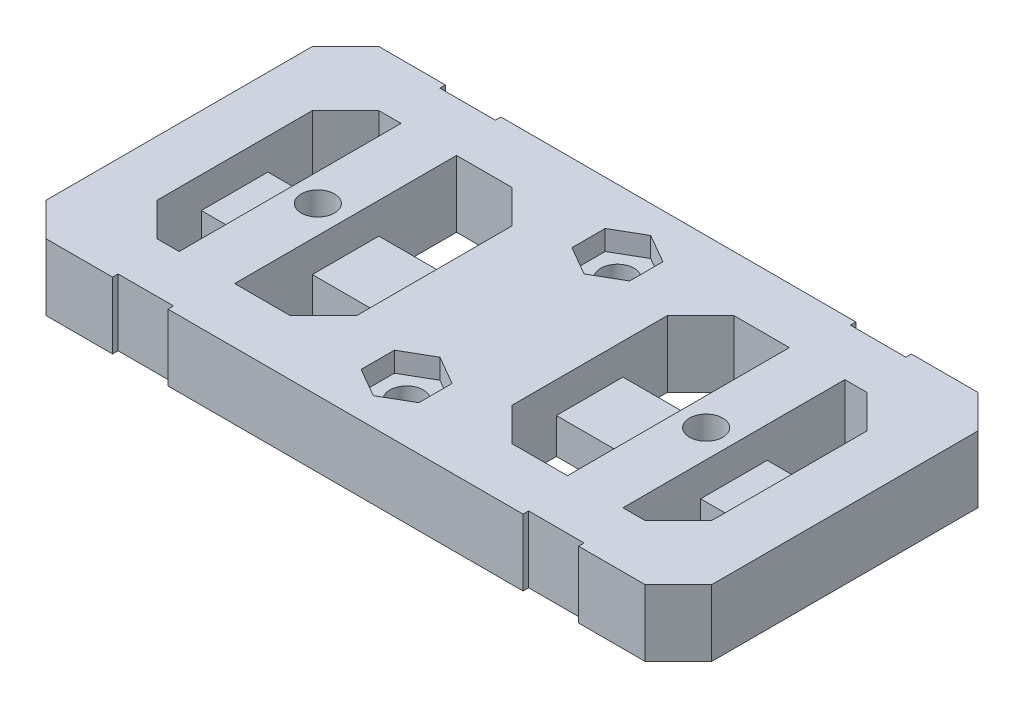
SolidWorks part; units mm, degrees
ref_plane "정면" through (0, 0, 0) normal (0, 0, 1) x (1, 0, 0)
ref_plane "윗면" through (0, 0, 0) normal (0, 1, 0) x (1, 0, 0)
ref_plane "우측면" through (0, 0, 0) normal (1, 0, 0) x (0, 0, -1)
sketch "스케치1" plane through (0, 0, 0) normal (0, 1, 0) x (1, 0, 0)
  line L0 (0, -9.5) -> (0, 9.5) construction
  line L1 (25, 10) -> (25, -10)
  line L2 (0, 12.5022) -> (-2.6, 11.0011)
  line L3 (-2.6, 11.0011) -> (-2.6, 7.9989)
  line L4 (-2.6, 7.9989) -> (0, 6.4978)
  line L5 (0, 6.4978) -> (2.6, 7.9989)
  line L6 (2.6, 7.9989) -> (2.6, 11.0011)
  line L7 (2.6, 11.0011) -> (0, 12.5022)
  line L8 (0, -6.4978) -> (-2.6, -7.9989)
  line L9 (-2.6, -7.9989) -> (-2.6, -11.0011)
  line L10 (-2.6, -11.0011) -> (0, -12.5022)
  line L11 (0, -12.5022) -> (2.6, -11.0011)
  line L12 (2.6, -11.0011) -> (2.6, -7.9989)
  line L13 (2.6, -7.9989) -> (0, -6.4978)
  line L14 (-30, -15) -> (30, -15)
  line L15 (-30, -15) -> (-30, 15)
  line L16 (-30, 15) -> (30, 15)
  line L17 (30, -15) -> (30, 15)
  line L18 (-30, -15) -> (30, 15) construction
  line L19 (-30, 15) -> (30, -15) construction
  line L20 (-25, 10) -> (-7, 10)
  line L21 (-25, 10) -> (-25, -10)
  line L22 (-25, -10) -> (-7, -10)
  line L23 (-7, 10) -> (-7, -10)
  line L24 (25, 10) -> (7, 10)
  line L25 (7, 10) -> (7, -10)
  line L26 (25, -10) -> (7, -10)
  circle A0 centre (0, 9.5) radius 1.5
  circle A1 centre (0, -9.5) radius 1.5
  circle A2 centre (0, 9.5) radius 2.6 construction
  circle A3 centre (0, -9.5) radius 2.6 construction
  point P4 (0, 0)
  point P7 (0, 0)
  point P34 (-7, 0)
  point P35 (7, 0)
  point P36 (-30, 0)
  point P37 (30, 0)
  dimension "D2" = 3
  dimension "D1" = 19
  dimension "D3" = 5.2
  dimension "D4" = 30
  dimension "D5" = 60
  dimension "D6" = 18
  dimension "D7" = 20
  dimension "D8" = 5
extrude "보스-돌출1" add sketch "스케치1" along normal blind 3 contours L14 L17 L16 L15 L7 L6 L5 L4 L3 L2 L13 L12 L11 L10 L9 L8 L20 L23 L22 L21 L1 L26 L25 L24 | L12 L13 L8 L9 L10 L11 A1 | L6 L7 L2 L3 L4 L5 A0 region at (1.2603, 0, -11.6829) region at (1.2603, 0, 7.3171) region at (0, 0, 0)
extrude "컷-돌출1" cut sketch "스케치1<3>" against normal blind 1.8 from surface contours L12 L13 L8 L9 L10 L11 A1 | L6 L7 L2 L3 L4 L5 A0 region at (1.2603, 0, -11.6829) region at (1.2603, 0, 7.3171) starting at face at (0, 3, 0)
sketch "스케치1<3>" plane through (0, 0, 0) normal (0, 1, 0) x (1, 0, 0) same geometry as "스케치1"
chamfer "모따기1" distance 3 angle 45 12 edges at (25, 1.5, -10) (25, 1.5, 10) (7, 1.5, 10) (7, 1.5, -10) (-25, 1.5, 10) (-7, 1.5, 10) (-7, 1.5, -10) (-25, 1.5, -10) (30, 1.5, -15) (30, 1.5, 15) (-30, 1.5, 15) (-30, 1.5, -15)
sketch "스케치2" plane through (0, 3, 0) normal (0, 1, 0) x (1, 0, 0)
  line L0 (0, 45) -> (0, -15)
  line L2 (-27, -15) -> (27, -15) construction
  line L3 (-27, 15) -> (27, 15) construction
  line L4 (-21, 15) -> (-16, 15)
  line L5 (-21, 15) -> (-21, 14.5)
  line L6 (-21, 14.5) -> (-16, 14.5)
  line L7 (-16, 15) -> (-16, 14.5)
  line L8 (21, 15) -> (21, 14.5)
  line L9 (21, 15) -> (16, 15)
  line L10 (16, 15) -> (16, 14.5)
  line L11 (21, 14.5) -> (16, 14.5)
  line L12 (21, -15) -> (21, -14.5)
  line L13 (-21, -15) -> (-16, -15)
  line L14 (-21, -15) -> (-21, -14.5)
  line L15 (-21, -14.5) -> (-16, -14.5)
  line L16 (-16, -15) -> (-16, -14.5)
  line L17 (21, -15) -> (16, -15)
  line L18 (16, -15) -> (16, -14.5)
  line L19 (21, -14.5) -> (16, -14.5)
  line L20 (-30, -12) -> (-30, 12) construction
  point P3 (0, 15)
  line M16 (27, 15) -> (-27, 15)
  line M20 (-27, -15) -> (27, -15)
  dimension "D1" = 0.5
  dimension "D2" = 9
  dimension "D3" = 5
extrude "컷-돌출2" cut sketch "스케치2" against normal through all contours L16 L15 L14 M20 | L12 L19 L18 M20 | L11 L8 L10 M16 | L4 L7 L6 L5 region at (18.5, 3, 14.75) region at (-18.5, 3, 14.75) region at (18.5, 3, -14.75)
sketch "스케치3" plane through (0, 3, 0) normal (0, 1, 0) x (1, 0, 0)
  line L0 (0, 15) -> (0, -15) construction
  line L1 (-16, 15) -> (16, 15) construction
  line L2 (-16, -15) -> (16, -15) construction
  line L3 (-30, 0) -> (30, 0) construction
  line L4 (-30, -12) -> (-30, 12) construction
  line L5 (30, -12) -> (30, 12) construction
  line L6 (-22, 10) -> (-10, 10) construction
  line L7 (-20, -10) -> (-15, -10)
  line L8 (-20, -10) -> (-20, 10)
  line L9 (-20, 10) -> (-15, 10)
  line L10 (-15, -10) -> (-15, 10)
  line L11 (-20, -10) -> (-15, 10) construction
  line L12 (-20, 10) -> (-15, -10) construction
  line L13 (20, -10) -> (15, 10) construction
  line L14 (20, 10) -> (15, -10) construction
  line L15 (20, -10) -> (20, 10)
  line L16 (20, -10) -> (15, -10)
  line L17 (15, -10) -> (15, 10)
  line L18 (20, 10) -> (15, 10)
  circle A0 centre (-17.5, 0) radius 1.5
  circle A1 centre (17.5, 0) radius 1.5
  point P24 (17.5, 0)
  dimension "D1" = 3
  dimension "D2" = 35
  dimension "D3" = 5
extrude "보스-돌출2" add sketch "스케치3" against normal up to vertex (3 mm away) up to point (-10, 0, -10)
sketch "스케치4" plane through (0, 0, 0) normal (0, -1, 0) x (1, 0, 0)
  line L0 (-22, 10) -> (-20, 10) construction
  line L1 (-20, -10) -> (-20, 10) construction
  line L2 (-25, -7) -> (-25, 7) construction
  line L3 (-22, 10) -> (-20, 10)
  line L4 (-20, -10) -> (-20, 10)
  line L5 (-25, -7) -> (-25, 7)
  line L6 (-20, -10) -> (-20, 10)
  line L7 (-22, -10) -> (-20, -10)
  line L8 (-25, -7) -> (-22, -10)
  line L9 (-25, 7) -> (-25, -7)
  line L10 (-22, 10) -> (-25, 7)
  line L11 (-20, 10) -> (-22, 10)
  line L12 (-20, -10) -> (-20, 10)
  line L13 (-22, -10) -> (-20, -10)
  line L14 (-25, -7) -> (-22, -10)
  line L15 (-25, 7) -> (-25, -7)
  line L16 (-22, 10) -> (-25, 7)
  line L17 (-20, 10) -> (-22, 10)
  line L18 (-15, -10) -> (-10, -10)
  line L19 (-15, 10) -> (-15, -10)
  line L20 (-10, 10) -> (-15, 10)
  line L21 (-7, 7) -> (-10, 10)
  line L22 (-7, -7) -> (-7, 7)
  line L23 (-10, -10) -> (-7, -7)
  line L24 (-27, -15) -> (-21, -15)
  line L25 (-21, -15) -> (-21, -14.5)
  line L26 (-21, -14.5) -> (-16, -14.5)
  line L27 (-16, -14.5) -> (-16, -15)
  line L28 (-16, -15) -> (16, -15)
  line L29 (16, -15) -> (16, -14.5)
  line L30 (16, -14.5) -> (21, -14.5)
  line L31 (21, -14.5) -> (21, -15)
  line L32 (21, -15) -> (27, -15)
  line L33 (27, -15) -> (30, -12)
  line L34 (30, -12) -> (30, 12)
  line L35 (30, 12) -> (27, 15)
  line L36 (27, 15) -> (21, 15)
  line L37 (21, 15) -> (21, 14.5)
  line L38 (21, 14.5) -> (16, 14.5)
  line L39 (16, 14.5) -> (16, 15)
  line L40 (16, 15) -> (-16, 15)
  line L41 (-16, 15) -> (-16, 14.5)
  line L42 (-16, 14.5) -> (-21, 14.5)
  line L43 (-21, 14.5) -> (-21, 15)
  line L44 (-21, 15) -> (-27, 15)
  line L45 (-27, 15) -> (-30, 12)
  line L46 (-30, 12) -> (-30, -12)
  line L47 (-30, -12) -> (-27, -15)
  line L48 (-27, -15) -> (-21, -15)
  line L49 (-21, -15) -> (-21, -14.5)
  line L50 (-21, -14.5) -> (-16, -14.5)
  line L51 (-16, -14.5) -> (-16, -15)
  line L52 (-16, -15) -> (16, -15)
  line L53 (16, -15) -> (16, -14.5)
  line L54 (16, -14.5) -> (21, -14.5)
  line L55 (21, -14.5) -> (21, -15)
  line L56 (21, -15) -> (27, -15)
  line L57 (27, -15) -> (30, -12)
  line L58 (30, -12) -> (30, 12)
  line L59 (30, 12) -> (27, 15)
  line L60 (27, 15) -> (21, 15)
  line L61 (21, 15) -> (21, 14.5)
  line L62 (21, 14.5) -> (16, 14.5)
  line L63 (16, 14.5) -> (16, 15)
  line L64 (16, 15) -> (-16, 15)
  line L65 (-16, 15) -> (-16, 14.5)
  line L66 (-16, 14.5) -> (-21, 14.5)
  line L67 (-21, 14.5) -> (-21, 15)
  line L68 (-21, 15) -> (-27, 15)
  line L69 (-27, 15) -> (-30, 12)
  line L70 (-30, 12) -> (-30, -12)
  line L71 (-30, -12) -> (-27, -15)
  line L72 (-15, -10) -> (-10, -10)
  line L73 (-15, 10) -> (-15, -10)
  line L74 (-10, 10) -> (-15, 10)
  line L75 (-7, 7) -> (-10, 10)
  line L76 (-7, -7) -> (-7, 7)
  line L77 (-10, -10) -> (-7, -7)
  line L78 (15, 10) -> (10, 10)
  line L79 (15, -10) -> (15, 10)
  line L80 (10, -10) -> (15, -10)
  line L81 (7, -7) -> (10, -10)
  line L82 (7, 7) -> (7, -7)
  line L83 (10, 10) -> (7, 7)
  line L84 (15, 10) -> (10, 10)
  line L85 (15, -10) -> (15, 10)
  line L86 (10, -10) -> (15, -10)
  line L87 (7, -7) -> (10, -10)
  line L88 (7, 7) -> (7, -7)
  line L89 (10, 10) -> (7, 7)
  line L90 (20, 10) -> (20, -10)
  line L91 (22, 10) -> (20, 10)
  line L92 (25, 7) -> (22, 10)
  line L93 (25, -7) -> (25, 7)
  line L94 (22, -10) -> (25, -7)
  line L95 (20, -10) -> (22, -10)
  line L96 (20, 10) -> (20, -10)
  line L97 (22, 10) -> (20, 10)
  line L98 (25, 7) -> (22, 10)
  line L99 (25, -7) -> (25, 7)
  line L100 (22, -10) -> (25, -7)
  line L101 (20, -10) -> (22, -10)
  line L102 (-30, 0) -> (30, 0) construction
  line L103 (-25, -3) -> (25, -3)
  line L104 (-25, -3) -> (-25, 3)
  line L105 (-25, 3) -> (25, 3)
  line L106 (25, -3) -> (25, 3)
  circle A0 centre (0, 9.5) radius 2.75
  circle A1 centre (-17.5, 0) radius 1.5
  circle A2 centre (-17.5, 0) radius 1.5
  circle A3 centre (17.5, 0) radius 1.5
  circle A4 centre (17.5, 0) radius 1.5
  circle A5 centre (0, -9.5) radius 1.5
  circle A6 centre (0, -9.5) radius 1.5
  circle A7 centre (0, 9.5) radius 1.5
  circle A8 centre (0, 9.5) radius 1.5
  circle A9 centre (0, -9.5) radius 2.75
  circle A10 centre (-17.5, 0) radius 2.75
  circle A11 centre (17.5, 0) radius 2.75
  dimension "D10" = 5.5
  dimension "D11" = 6
  dimension "D1" = 0
  dimension "D2" = 0
  dimension "D3" = 0
  dimension "D4" = 0
  dimension "D5" = 0
  dimension "D6" = 0
  dimension "D7" = 0
  dimension "D8" = 0
  dimension "D9" = 0
extrude "보스-돌출3" add sketch "스케치4" along normal blind 3 contours L70 L102 L104 L5 L16 L3 L4 L105 L73 L74 L75 L76 L88 L89 L84 L85 L96 L97 L98 L99 L106 L58 L59 L60 L61 L62 L63 L64 L65 L66 L67 L68 L69 A0 | L102 L70 L71 L48 L49 L50 L51 L52 L53 L54 L55 L56 L57 L58 L99 L100 L101 L96 L103 L85 L86 L87 L88 L76 L77 L72 L73 L4 L13 L14 L5 L15 A9 | L76 L102 L88 L105 | L102 L76 L103 L88 | L104 L102 A10 L12 L105 | L102 L15 L103 L12 A10 | A10 L73 L105 L12 | A10 L102 L76 L105 L73 | A10 L12 L103 L73 | L102 A10 L73 L103 L76 | L88 L102 A11 L85 L105 | L102 L88 L103 L85 A11 | A11 L96 L105 L85 | A11 L85 L103 L96 | L102 A11 L96 L103 L99 | A11 L102 L106 L105 L96 region at (-23.9373, 0, 8.9373) region at (-17.5, 0, 2.9467) region at (-22.5312, 0, 1.5139) region at (-10.9684, 0, 1.5086) region at (-22.5312, 0, -1.5139) region at (-25.6185, 0, -1.5) region at (0, 0, 1.5) region at (-17.5, 0, -2.8033) region at (-10.9684, 0, -1.5086) region at (0, 0, -1.5) region at (10.9684, 0, 1.5086) region at (10.9684, 0, -1.5086) region at (17.5, 0, 2.9467) region at (22.5312, 0, 1.5139) region at (15.0533, 0, -2.0728) region at (22.5312, 0, -1.5139)
extrude "보스-돌출4" add sketch "스케치4<3>" against normal blind 0.2 contours L96 L102 A11 | L102 L96 A11 | L102 A11 L96 L103 L99 | A11 L102 L106 L105 L96 | A11 L102 L85 | L102 A11 L85 | L102 L88 L103 L85 A11 | L88 L102 A11 L85 L105 | A10 L102 L12 | L102 A10 L4 | L102 L15 L103 L12 A10 | L104 L102 A10 L12 L105 | A10 L102 L76 L105 L73 | L102 A10 L73 L103 L76 | L73 L102 A10 | L102 L73 A10 region at (-22.5312, 0, 1.5139) region at (-20.1004, 0, 0.4323) region at (-10.9684, 0, 1.5086) region at (-22.5312, 0, -1.5139) region at (-20.1004, 0, -0.4323) region at (-14.8996, 0, 0.4323) region at (-14.8996, 0, -0.4323) region at (-10.9684, 0, -1.5086) region at (10.9684, 0, 1.5086) region at (10.9684, 0, -1.5086) region at (14.8996, 0, 0.4323) region at (14.8996, 0, -0.4323) region at (22.5312, 0, 1.5139) region at (20.1004, 0, 0.4323) region at (22.5312, 0, -1.5139) region at (20.1004, 0, -0.4323)
sketch "스케치4<3>" plane through (0, 0, 0) normal (0, -1, 0) x (1, 0, 0) same geometry as "스케치4"
